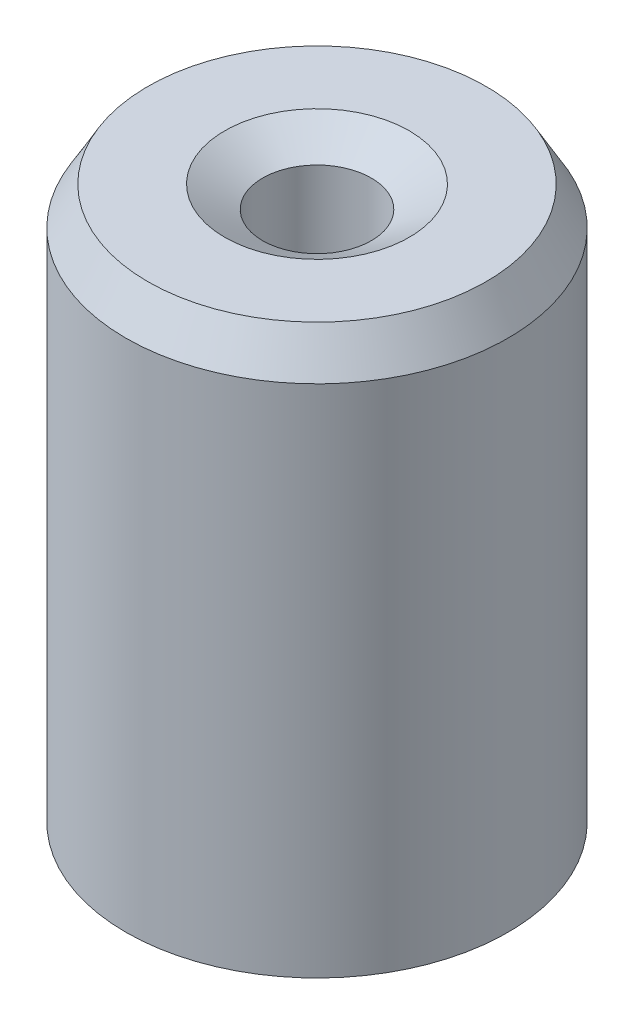
SolidWorks part; units mm, degrees
ref_plane "Front Plane" through (0, 0, 0) normal (0, 0, 1) x (1, 0, 0)
ref_plane "Top Plane" through (0, 0, 0) normal (0, 1, 0) x (1, 0, 0)
ref_plane "Right Plane" through (0, 0, 0) normal (1, 0, 0) x (0, 0, -1)
sketch "Sketch1" plane through (0, 0, 0) normal (0, 1, 0) x (1, 0, 0)
  circle A0 centre (0, 0) radius 5
  dimension "SLEEVE_OD" = 10
extrude "Boss-Extrude1" add sketch "Sketch1" along normal blind 15.0318
sketch "Sketch2" plane through (0, 0, 0) normal (0, 1, 0) x (1, 0, 0)
  circle A0 centre (0, 0) radius 1.4218
  dimension "BORE_D" = 2.8437
extrude "Cut-Extrude1" cut sketch "Sketch2" along normal through all
chamfer "Chamfer1" distance 0.9932 angle 30 4 edges at (0, 15.0318, 1.4218) (0, 0, 1.4218) (0, 0, 5) (0, 15.0318, 5) first distance on face at (0, 15.0318, 1.4218) first distance on face at (0, 0, 1.4218) first distance on face at (0, 15.0318, 5)
